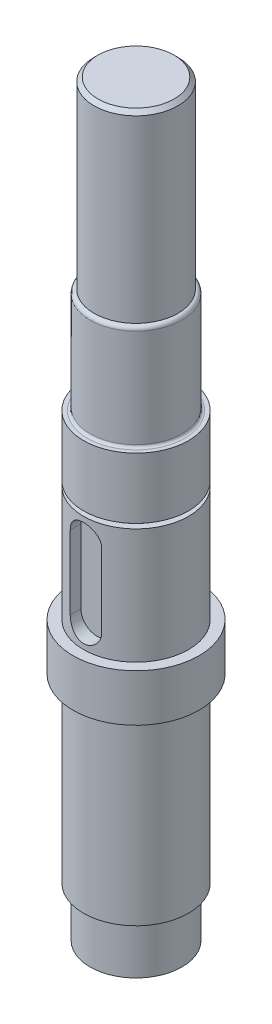
SolidWorks part; units mm, degrees
ref_plane "Front Plane" through (0, 0, 0) normal (0, 0, 1) x (1, 0, 0)
ref_plane "Top Plane" through (0, 0, 0) normal (0, 1, 0) x (1, 0, 0)
ref_plane "Right Plane" through (0, 0, 0) normal (1, 0, 0) x (0, 0, -1)
sketch "Sketch1" plane through (0, 0, 0) normal (0, 0, 1) x (1, 0, 0)
  line L0 (0, 0) -> (0, 98.7831) construction
  line L1 (0, 0) -> (17.5, 0)
  line L2 (17.5, 0) -> (17.5, 19)
  line L3 (17.5, 19) -> (20, 19)
  line L4 (20, 19) -> (20, 88)
  line L5 (20, 88) -> (24, 88)
  line L6 (24, 88) -> (24, 106)
  line L7 (24, 106) -> (20, 106)
  line L8 (20, 106) -> (20, 150)
  line L9 (20, 150) -> (17.5, 150)
  line L10 (17.5, 150) -> (17.5, 151.8)
  line L11 (17.5, 151.8) -> (20, 151.8)
  line L12 (20, 151.8) -> (20, 175)
  line L13 (20, 175) -> (17.5, 175)
  line L14 (17.5, 175) -> (17.5, 215)
  line L15 (17.5, 215) -> (16, 215)
  line L16 (16, 215) -> (16, 285)
  line L17 (16, 285) -> (0, 285)
  line L18 (0, 98.7831) -> (0, 285) construction
  line L19 (0, 0) -> (0, 285)
  point P18 (0, 0)
  point P21 (0, 0)
  point P22 (0, 0)
  point P23 (0, 0)
  point P24 (0, 0)
  dimension "D1" = 17.5
  dimension "D2" = 20
  dimension "D3" = 285
  dimension "D4" = 19
  dimension "D5" = 69
  dimension "D6" = 18
  dimension "D7" = 44
  dimension "D8" = 1.8
  dimension "D9" = 25
  dimension "D10" = 40
  dimension "D11" = 70
  dimension "D12" = 16
  dimension "D13" = 24
revolve "Revolve1" add sketch "Sketch1" angle 360 about L19
chamfer "Chamfer1" distance 1.5 angle 45 1 edges at (16, 285, 0)
fillet "Fillet2" radius 1.5 1 edges at (17.5, 215, 0)
ref_plane "Plane1" through (0, 0, 20) normal (0, 0, 1) x (1, 0, 0)
sketch "Sketch3" plane through (0, 0, 20) normal (0, 0, 1) x (1, 0, 0)
  line L0 (0, 142) -> (0, 114) construction
  line L1 (6, 142) -> (6, 114)
  line L2 (-6, 142) -> (-6, 114)
  arc A0 (6, 142) -> (-6, 142) centre (0, 142) ccw
  arc A1 (-6, 114) -> (6, 114) centre (0, 114) ccw
  point P3 (0, 128)
  point P8 (0, 148)
  point P9 (0, 108)
  dimension "D2" = 6
  dimension "D1" = 40
  dimension "D3" = 2
extrude "Cut-Extrude1" cut sketch "Sketch3" against normal blind 5
ref_plane "Plane2" through (-16, 0, 0) normal (1, 0, 0) x (0, 0, -1)
sketch "Sketch4" plane through (-16, 0, 0) normal (1, 0, 0) x (0, 0, -1)
  line L0 (0, 267.5) -> (0, 237.5) construction
  line L1 (10, 267.5) -> (10, 237.5)
  line L2 (-10, 267.5) -> (-10, 237.5)
  arc A0 (10, 267.5) -> (-10, 267.5) centre (0, 267.5) ccw
  arc A1 (-10, 237.5) -> (10, 237.5) centre (0, 237.5) ccw
  point P3 (0, 252.5)
  point P8 (0, 277.5)
  point P9 (0, 227.5)
  dimension "D3" = 10
  dimension "D1" = 50
  dimension "D2" = 7.5
extrude "Cut-Extrude2" cut sketch "Sketch4" along normal blind 5
fillet "Fillet4" radius 1 1 edges at (17.5, 175, 0)
